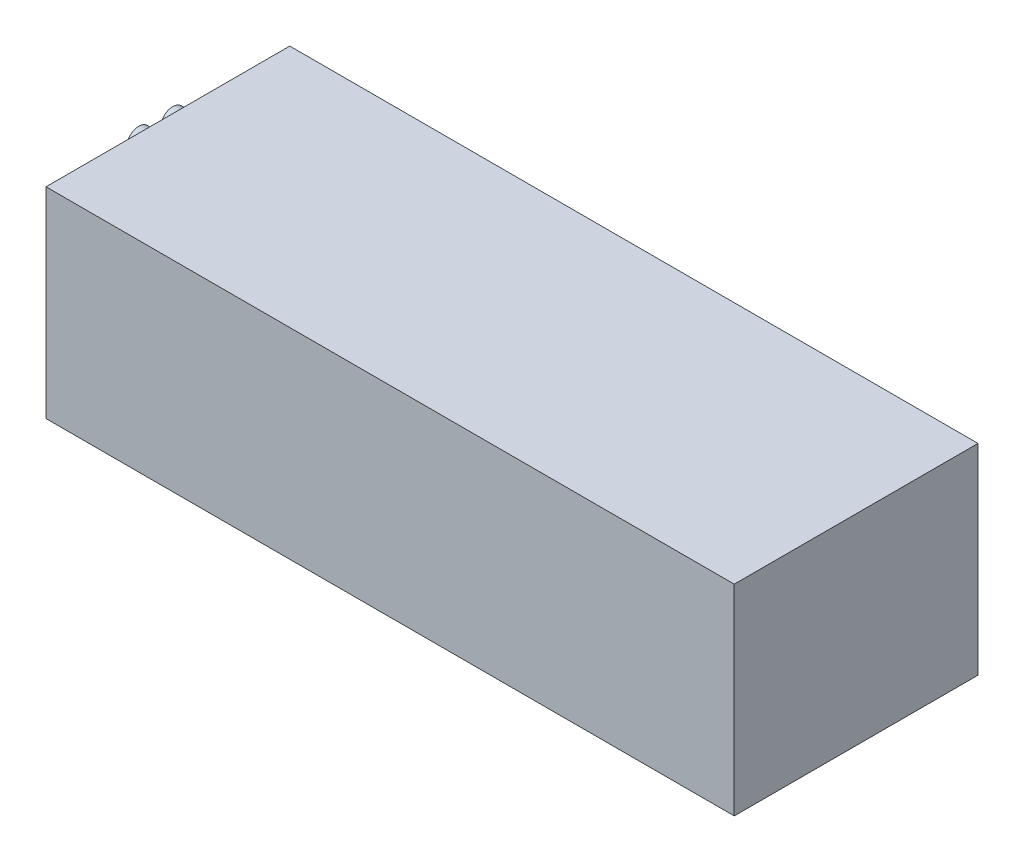
SolidWorks part; units mm, degrees
ref_plane "Front Plane" through (0, 0, 0) normal (0, 0, 1) x (1, 0, 0)
ref_plane "Top Plane" through (0, 0, 0) normal (0, 1, 0) x (1, 0, 0)
ref_plane "Right Plane" through (0, 0, 0) normal (1, 0, 0) x (0, 0, -1)
other "Center of Mass"
sketch "Sketch1" plane through (0, 0, 0) normal (0, 1, 0) x (1, 0, 0)
  line L5 (-72, -25.5) -> (72, -25.5)
  line L6 (-72, -25.5) -> (-72, 25.5)
  line L7 (-72, 25.5) -> (72, 25.5)
  line L8 (72, -25.5) -> (72, 25.5)
  line L9 (-72, -25.5) -> (72, 25.5) construction
  line L10 (-72, 25.5) -> (72, -25.5) construction
  point P0 (0, 0)
  dimension "D1" = 144
  dimension "D2" = 51
extrude "Boss-Extrude1" add sketch "Sketch1" along normal blind 41.9999 contours L7 L8 L5 L6
sketch "Sketch2" plane through (-72, 0, 0) normal (-1, 0, 0) x (0, 0, 1)
  line L0 (0, -23.1) -> (0, 23.1) construction
  line L1 (25.5, 41.9999) -> (-25.5, 41.9999) construction
  circle A0 centre (-3.556, 38.1899) radius 2.54
  circle A1 centre (3.556, 38.1899) radius 2.54
  dimension "D2" = 5.08
  dimension "D1" = 3.556
  dimension "D3" = 3.81
extrude "Boss-Extrude2" add sketch "Sketch2" along normal blind 2.54
sketch "Sketch3" plane through (-74.54, 0, 0) normal (-1, 0, 0) x (0, 0, 1)
  point P0 (3.556, 38.1899)
  point P1 (-3.556, 38.1899)
ref_plane "Plane1" through (-78.35, 0, 0) normal (-1, 0, 0) x (0, 0, 1)
sketch "Sketch4" plane through (-78.35, 0, 0) normal (-1, 0, 0) x (0, 0, 1)
  point P0 (-3.556, 38.1899)
  point P1 (3.556, 38.1899)
equation "\"Batt_Length\"=6"
equation "\"Batt_Height\"=2"
equation "\"Batt_Depth\"=1.65354"
equation "\"D1@Boss-Extrude1\"=\"Batt_Depth\""
